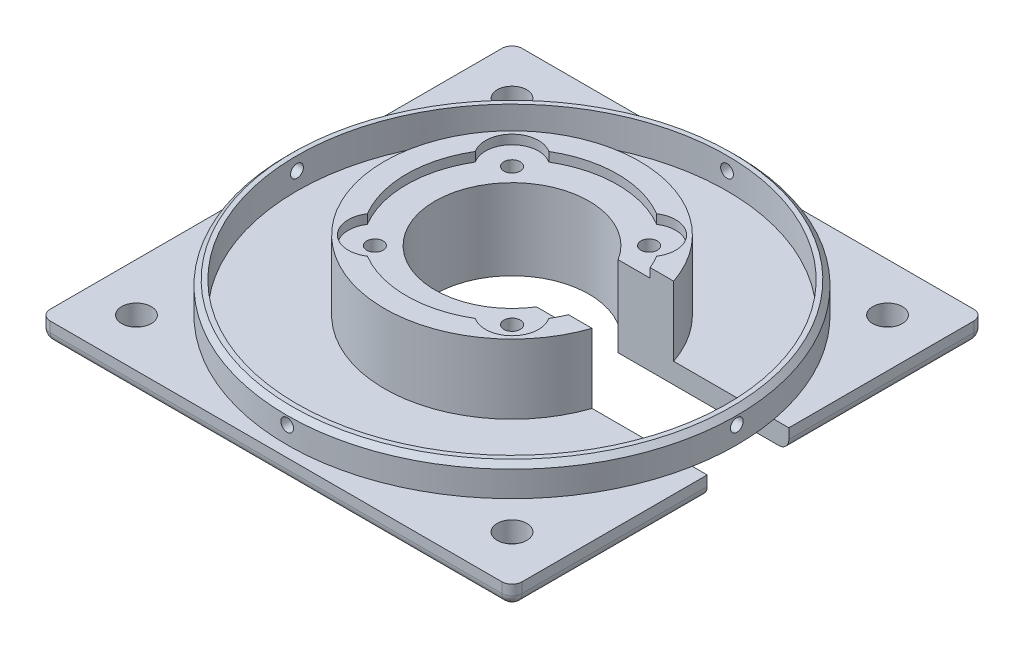
SolidWorks part; units mm, degrees
ref_plane "Front Plane" through (0, 0, 0) normal (0, 0, 1) x (1, 0, 0)
ref_plane "Top Plane" through (0, 0, 0) normal (0, 1, 0) x (1, 0, 0)
ref_plane "Right Plane" through (0, 0, 0) normal (1, 0, 0) x (0, 0, -1)
sketch "Sketch3" plane through (0, 0, 0) normal (0, 1, 0) x (1, 0, 0)
  circle A0 centre (0, 0) radius 7.55
  circle A1 centre (0, 0) radius 12.5
  dimension "D1" = 15.1
  dimension "D2" = 25
extrude "Boss-Extrude2" add sketch "Sketch3" along normal blind 8.8
sketch "Sketch4" plane through (0, 8.8, 0) normal (0, 1, 0) x (1, 0, 0)
  line L0 (6.4033, 4) -> (6.4033, -4)
  line L1 (6.4033, -4) -> (13.2817, -4)
  line L2 (13.2817, -4) -> (13.2817, 4)
  line L3 (13.2817, 4) -> (6.4033, 4)
  circle A0 centre (0, 0) radius 7.55 construction
  point P0 (0, 0)
  point P1 (6.4033, 4)
  point P3 (6.4033, -4)
  dimension "D1" = 4
extrude "Cut-Extrude2" cut sketch "Sketch4" against normal blind 8.8
sketch "Sketch5" plane through (0, 8.8, 0) normal (0, 1, 0) x (1, 0, 0)
  line L0 (0, 0) -> (17.4279, 0) construction
  line L1 (0, 0) -> (-11.2462, -11.2462) construction
  line L2 (0, 0) -> (-11.0539, 11.0539) construction
  point P0 (0, 0)
  point P1 (-6.715, 6.72)
  point P3 (-6.715, -6.72)
  point P9 (6.72, -6.715)
  point P10 (6.72, 6.715)
  dimension "D1" = 6.72
  dimension "D2" = 9.5
  dimension "D3" = 6.72
  dimension "D4" = 9.5
sketch "Sketch6" plane through (0, 8.8, 0) normal (0, 1, 0) x (1, 0, 0)
  line L0 (0, 0) -> (-11.2462, -11.2462) construction
  line L1 (0, 0) -> (-11.0539, 11.0539) construction
  line L2 (0, 0) -> (17.4279, 0) construction
  point P0 (5.2883, -8.8853)
  point P9 (-8.8853, 5.2883)
  point P12 (5.2883, 8.8853)
  point P14 (8.8893, -5.2817)
  point P15 (-5.2817, 8.8893)
  point P16 (8.8893, 5.2817)
  point P17 (-5.2817, -8.8893)
  point P18 (-8.8853, -5.2883)
  dimension "D1" = 2.6
  dimension "D2" = 10.34
  dimension "D3" = 2.6
  dimension "D4" = 10.34
sketch "Sketch8" plane through (0, 8.8, 0) normal (0, 1, 0) x (1, 0, 0)
  circle A0 centre (0, 0) radius 10.34
extrude "Cut-Extrude5" cut sketch "Sketch8" against normal blind 0.9
hole_wizard "Tap Drill for M2x0.4 Tap1" positions "3DSketch1" profile "Sketch10" hole size "M2x0.4" standard "ANSI Metric" end condition through all
sketch3d "3DSketch1"
  point P0 (6.72, 8.8, 6.715)
  point P3 (-6.715, 8.8, 6.72)
  point P6 (-6.715, 8.8, -6.72)
  point P9 (6.72, 8.8, -6.715)
sketch "Sketch10" plane through (6.72, 8.8, 6.715) normal (1, 0, 0) x (0, 0, 1)
  line L0 (0, 0) -> (0, 8.8)
  line L1 (0, 8.8) -> (0.8, 8.8)
  line L2 (0.8, 8.8) -> (0.8, 0)
  line L5 (0.8, 0) -> (0, 0)
  line L11 (0, -6.35) -> (0, 107.95) construction
  dimension "Thru Hole Dia." = 1.6
  dimension "Thru Hole Depth" = 8.8
sketch "Sketch11" plane through (0, 8.8, 0) normal (0, 1, 0) x (1, 0, 0)
  line L0 (8.8893, 5.2817) -> (5.2883, 8.8853)
  line L1 (8.8893, -5.2817) -> (5.2883, -8.8853)
  line L2 (-5.2817, -8.8893) -> (-8.8853, -5.2883)
  line L3 (-5.2817, 8.8893) -> (-8.8853, 5.2883)
  arc A0 (5.2883, -8.8853) -> (8.8893, -5.2817) centre (6.72, -6.715) ccw
  arc A1 (9.535, 4) -> (9.535, -4) centre (0, 0) ccw construction
  arc A2 (8.8893, 5.2817) -> (5.2883, 8.8853) centre (6.72, 6.715) ccw
  arc A3 (-5.2817, 8.8893) -> (-8.8853, 5.2883) centre (-6.715, 6.72) ccw
  arc A4 (-8.8853, -5.2883) -> (-5.2817, -8.8893) centre (-6.715, -6.72) ccw
extrude "Cut-Extrude6" cut sketch "Sketch11" against normal blind 0.9
sketch "Sketch12" plane through (0, 0, 0) normal (0, -1, 0) x (1, 0, 0)
  line L0 (0, 0) -> (17.7684, 0) construction
  line L1 (0, 0) -> (0, 18.0241) construction
  line L2 (23.125, -23.125) -> (-23.125, -23.125)
  line L3 (-23.125, -23.125) -> (-23.125, 23.125)
  line L4 (-23.125, 23.125) -> (23.125, 23.125)
  line L9 (6.4033, 4) -> (23.125, 4)
  line L11 (23.125, -4) -> (6.4033, -4)
  line L13 (23.125, -23.125) -> (23.125, -4)
  line L14 (23.125, 23.125) -> (23.125, 4)
  arc A0 (6.4033, -4) -> (6.4033, 4) centre (0, 0) cw
  arc A1 (6.4033, 4) -> (6.4033, -4) centre (0, 0) ccw construction
  point P0 (23.125, -23.125)
  point P4 (23.125, 23.125)
  point P5 (-23.125, 23.125)
  point P7 (-23.125, -23.125)
  dimension "D1" = 23.125
  dimension "D2" = 23.125
extrude "Boss-Extrude4" add sketch "Sketch12" against normal blind 2
fillet "Fillet2" radius 1 2 edges at (-23.125, 0, 0) (0, 0, 23.125)
fillet "Fillet3" radius 1 2 edges at (-22.8321, 0.2929, 22.8321) (-23.125, 1.5, 23.125)
sketch "Sketch13" plane through (0, 0, 0) normal (0, -1, 0) x (1, 0, 0)
  line L0 (0, 0) -> (-25.0462, 0) construction
  line L1 (0, 0) -> (0, 26.5218) construction
  point P0 (18.3989, -18.3989)
  point P5 (18.3989, 18.3989)
  point P6 (-18.3989, -18.3989)
  point P7 (-18.3989, 18.3989)
  dimension "D1" = 18.3989
  dimension "D2" = 18.3989
hole_wizard "M2.5 Clearance Hole1" positions "3DSketch2" profile "Sketch14" hole size "M2.5" standard "ANSI Metric" end condition through all
sketch3d "3DSketch2"
  point P0 (18.3989, 0, 18.3989)
  point P3 (18.3989, 0, -18.3989)
  point P6 (-18.3989, 0, -18.3989)
  point P9 (-18.3989, 0, 18.3989)
sketch "Sketch14" plane through (18.3989, 0, 18.3989) normal (1, 0, 0) x (0, 0, -1)
  line L0 (0, 0) -> (0, 8.8)
  line L1 (0, 8.8) -> (1.45, 8.8)
  line L2 (1.45, 8.8) -> (1.45, 0)
  line L5 (1.45, 0) -> (0, 0)
  line L11 (0, -6.35) -> (0, 107.95) construction
  dimension "Thru Hole Dia." = 2.9
  dimension "Thru Hole Depth" = 8.8
fillet "Fillet4" radius 1 7 edges at (23.125, 1.5, 23.125) (23.125, 0.2929, 22.8321) (-23.125, 1.5, -23.125) (-22.8321, 0.2929, -23.125) (23.125, 0, 13.0625) (23.125, 0, -13.5625) (0.5, 0, -23.125)
fillet "Fillet5" radius 1 2 edges at (22.8321, 0.2929, -22.8321) (23.125, 1.5, -23.125)
sketch "Sketch15" plane through (0, 2, 0) normal (0, 1, 0) x (1, 0, 0)
  circle A0 centre (0, 0) radius 22.0375
  circle A1 centre (0, 0) radius 21.075
  point P0 (0, 0)
extrude "Boss-Extrude6" add sketch "Sketch15" along normal blind 3
hole_wizard "Tap Drill for M1.6x0.35 Tap1" positions "3DSketch4" profile "Sketch25" hole size "M1.6x0.35" standard "ANSI Metric" end condition up to next
sketch3d "3DSketch4"
  point P0 (22.0375, 3.7, 0)
  point P4 (0, 0, 0)
  point P5 (0, 0, 0)
  point P11 (0, 0, 0)
  point P12 (0, 0, 0)
  point P13 (0, 0, 0)
sketch "Sketch25" plane through (22.0375, 3.7, 0) normal (0, 1, 0) x (0, 0, -1)
  line L0 (0, 0) -> (0, 0.9625)
  line L1 (0, 0.9625) -> (0.625, 0.9625)
  line L2 (0.625, 0.9625) -> (0.625, 0)
  line L5 (0.625, 0) -> (0, 0)
  line L11 (0, -6.35) -> (0, 107.95) construction
  dimension "Thru Hole Dia." = 1.25
  dimension "Thru Hole Depth" = 0.9625
ref_axis "Axis1" through (0, 7.9, 0) along (0, -1, 0)
pattern_circular "CirPattern1" count 4 over 360 about axis through (0, 7.9, 0) along (0, -1, 0) of "Tap Drill for M1.6x0.35 Tap1"
chamfer "Chamfer1" distance 0.5 angle 45 1 edges at (0, 5, 22.0375)
